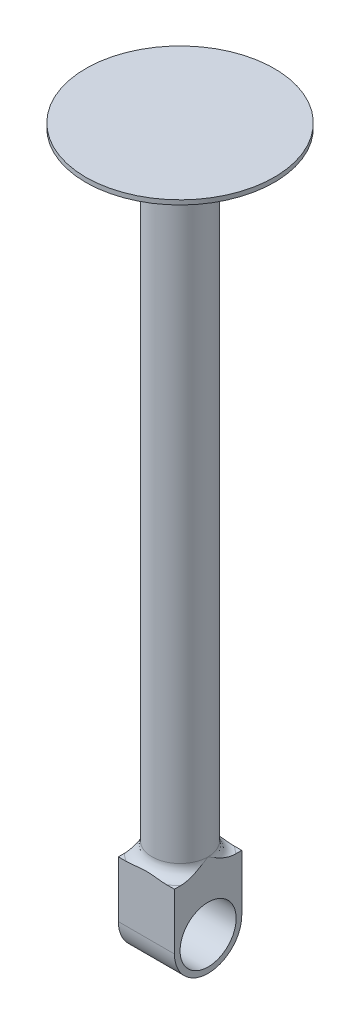
SolidWorks part; units mm, degrees
material "Hexcel AS4C (3000 Filaments)"
ref_plane "Front Plane" through (0, 0, 0) normal (0, 0, 1) x (1, 0, 0)
ref_plane "Top Plane" through (0, 0, 0) normal (0, 1, 0) x (1, 0, 0)
ref_plane "Right Plane" through (0, 0, 0) normal (1, 0, 0) x (0, 0, -1)
sketch "Sketch1" plane through (0, 0, 0) normal (1, 0, 0) x (0, 0, -1)
  line L0 (15, 0) -> (15, 305)
  line L1 (-15, 0) -> (-15, 305)
  line L2 (-15, 305) -> (15, 305)
  circle A0 centre (0, 0) radius 12.5
  circle A1 centre (0, 0) radius 15
  dimension "D1" = 25
  dimension "D2" = 30
  dimension "D3" = 305
extrude "Boss-Extrude1" add sketch "Sketch1" against normal blind 25 contours A1 L0 L2 L1 | A1 A0
sketch "Sketch2" plane through (0, 305, 0) normal (0, 1, 0) x (1, 0, 0)
  line L0 (0, 0) -> (-25, 0)
  line L1 (0, -15) -> (0, 15) construction
  line L2 (-25, -15) -> (-25, 15) construction
  line L3 (0, -15) -> (-25, -15)
  line L4 (-25, -15) -> (-25, 0)
  line L5 (0, -15) -> (0, 0)
  circle A0 centre (-12.5, 0) radius 12.5
  line M5 (0, -15) -> (0, 15)
  line M6 (0, 15) -> (-25, 15)
  line M7 (-25, 15) -> (-25, -15)
  line M8 (-25, -15) -> (0, -15)
extrude "Cut-Extrude1" cut sketch "Sketch2" against normal blind 280 contours A0 M7 M8 M5 | A0 M5 M6 M7
fillet "Fillet1" radius 5 1 edges at (-12.5, 25, 12.5) type face fillet first side face at (-12.5, 25, 10.625) second side face at (-12.5, 305, 12.5)
fillet "Fillet2" radius 5 3 edges at (-12.5, 25, -12.5) (-25, 27.5, 0) (0, 27.5, 0)
sketch "Sketch3" plane through (0, 305, 0) normal (0, 1, 0) x (1, 0, 0)
  circle A0 centre (-12.5, 0) radius 11.5
  dimension "D1" = 23
extrude "Cut-Extrude2" cut sketch "Sketch3" against normal blind 300
sketch "Sketch4" plane through (0, 305, 0) normal (0, 1, 0) x (1, 0, 0)
  line L0 (0, 0) -> (-25, 0)
  circle A0 centre (-12.5, 0) radius 12.5 construction
  circle A1 centre (-12.5, 0) radius 42
  dimension "D1" = 84
extrude "Boss-Extrude2" add sketch "Sketch4" along normal blind 2 contours A1
